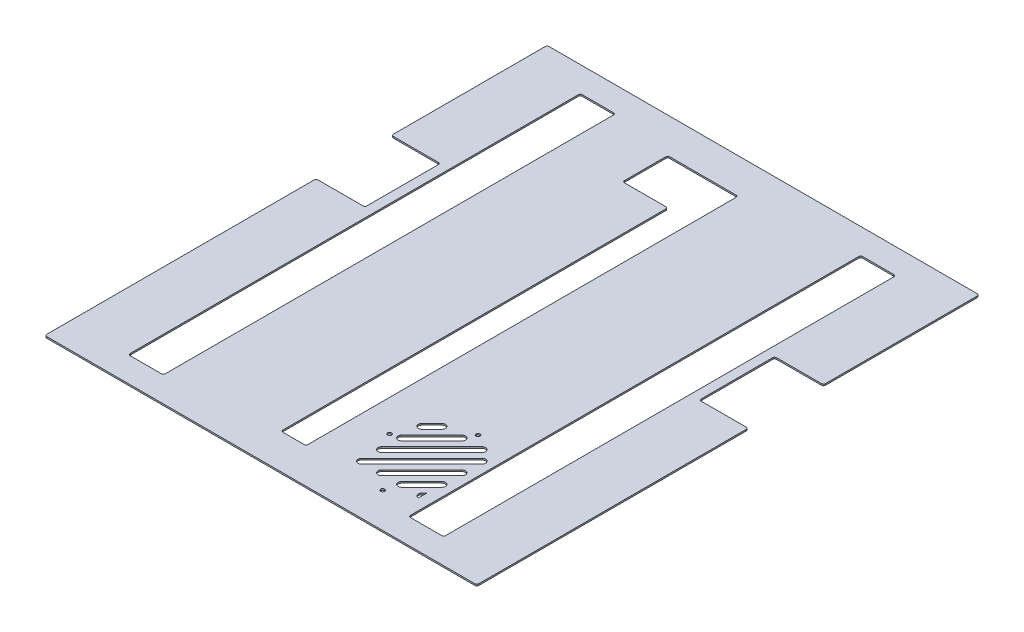
SolidWorks part; units mm, degrees
ref_plane "Front Plane" through (0, 0, 0) normal (0, 0, 1) x (1, 0, 0)
ref_plane "Top Plane" through (0, 0, 0) normal (0, 1, 0) x (1, 0, 0)
ref_plane "Right Plane" through (0, 0, 0) normal (1, 0, 0) x (0, 0, -1)
sketch "Sketch1" plane through (0, 0, 0) normal (0, 1, 0) x (1, 0, 0)
  line L1 (5911.0841, -8452.3124) -> (6341.0841, -8452.3124)
  line L2 (5911.0841, -8452.3124) -> (5911.0841, -8952.3124)
  line L3 (5911.0841, -8952.3124) -> (6341.0841, -8952.3124)
  line L4 (6341.0841, -8452.3124) -> (6341.0841, -8952.3124)
  dimension "D1" = 500
  dimension "D2" = 430
extrude "Boss-Extrude1" add sketch "Sketch1" along normal blind 1.5
sketch "Sketch2" plane through (0, 1.5, 0) normal (0, 1, 0) x (1, 0, 0)
  line L0 (5911.0841, -8452.3124) -> (5911.0841, -8952.3124) construction
  line L1 (5959.6841, -8682.3124) -> (5911.0841, -8682.3124)
  line L2 (5959.6841, -8682.3124) -> (5959.6841, -8607.3124)
  line L3 (5959.6841, -8607.3124) -> (5911.0841, -8607.3124)
  line L4 (5911.0841, -8682.3124) -> (5911.0841, -8607.3124)
  line L9 (6341.0841, -8952.3124) -> (6341.0841, -8452.3124) construction
  line L10 (6341.0841, -8682.3124) -> (6292.4841, -8682.3124)
  line L11 (6341.0841, -8682.3124) -> (6341.0841, -8607.3124)
  line L12 (6341.0841, -8607.3124) -> (6292.4841, -8607.3124)
  line L13 (6292.4841, -8682.3124) -> (6292.4841, -8607.3124)
  line L14 (6341.0841, -8452.3124) -> (5911.0841, -8452.3124) construction
  dimension "D1" = 48.6
  dimension "D2" = 75
  dimension "D3" = 75
  dimension "D4" = 48.6
  dimension "D5" = 155
extrude "Cut-Extrude1" cut sketch "Sketch2" against normal blind 10
sketch "Sketch3" plane through (0, 1.5, 0) normal (0, 1, 0) x (1, 0, 0)
  line L0 (5969.0841, -8541.6519) -> (5969.0841, -8927.3124)
  line L1 (6283.0841, -8927.3124) -> (6248.0841, -8927.3124)
  line L2 (6283.0841, -8927.3124) -> (6283.0841, -8477.3124)
  line L3 (6283.0841, -8477.3124) -> (6248.0841, -8477.3124)
  line L4 (6248.0841, -8927.3124) -> (6248.0841, -8477.3124)
  line L5 (5969.0841, -8477.3124) -> (6004.0841, -8477.3124)
  line L11 (5969.0841, -8927.3124) -> (6004.0841, -8927.3124)
  line L12 (6004.0841, -8477.3124) -> (6004.0841, -8927.3124)
  line L36 (5911.0841, -8682.3124) -> (5911.0841, -8952.3124) construction
  line L37 (6341.0841, -8952.3124) -> (6341.0841, -8682.3124) construction
  line L39 (6102.0841, -8487.3124) -> (6136.0841, -8487.3124)
  line L40 (6111.0841, -8532.3124) -> (6111.0841, -8917.3124)
  line L41 (6111.0841, -8917.3124) -> (6136.0841, -8917.3124)
  line L42 (6136.0841, -8487.3124) -> (6136.0841, -8917.3124)
  line L44 (6341.0841, -8452.3124) -> (5911.0841, -8452.3124) construction
  line L45 (5969.0841, -8477.3124) -> (5969.0841, -8541.6519)
  line L47 (5911.0841, -8952.3124) -> (6341.0841, -8952.3124) construction
  line L48 (6102.0841, -8487.3124) -> (6066.0841, -8487.3124)
  line L50 (6111.0841, -8532.3124) -> (6066.0841, -8532.3124)
  line L51 (6066.0841, -8487.3124) -> (6066.0841, -8532.3124)
  point P4 (6265.5841, -8477.3124)
  point P32 (6126.0841, -8452.3124)
  point P33 (6119.0841, -8487.3124)
  dimension "D15" = 35
  dimension "D22" = 45
  dimension "D1" = 35
  dimension "D3" = 35
  dimension "D4" = 25
  dimension "D5" = 25
  dimension "D6" = 58
  dimension "D7" = 45
  dimension "D8" = 58
  dimension "D9" = 205
  dimension "D10" = 35
  dimension "D11" = 200
  dimension "D20" = 25
  dimension "D21" = 25
extrude "Cut-Extrude2" cut sketch "Sketch3" against normal blind 10
sketch "Sketch4" plane through (0, 1.5, 0) normal (0, 1, 0) x (1, 0, 0)
  line L0 (6237.0841, -8848.0965) -> (6237.0841, -8858.0965) construction
  line L1 (6237.0841, -8898.0965) -> (6207.0841, -8898.0965) construction
  line L3 (6237.0841, -8833.0965) -> (6192.0841, -8833.0965) construction
  line L4 (6177.0841, -8898.0965) -> (6177.0841, -8848.0965) construction
  line L5 (5911.0841, -8952.3124) -> (6341.0841, -8952.3124) construction
  line L6 (6177.0841, -8898.0965) -> (6234.5841, -8840.5965)
  line L7 (6179.5841, -8885.5965) -> (6229.5841, -8835.5965)
  line L8 (6174.5841, -8880.5965) -> (6222.0841, -8833.0965)
  line L9 (6177.0841, -8898.0965) -> (6174.5841, -8900.5965)
  line L10 (6174.5841, -8880.5965) -> (6222.0841, -8833.0965)
  line L11 (6179.5841, -8865.5965) -> (6209.5841, -8835.5965)
  line L12 (6177.0841, -8898.0965) -> (6174.5841, -8900.5965) construction
  line L13 (6179.5841, -8865.5965) -> (6209.5841, -8835.5965)
  line L14 (6174.5841, -8860.5965) -> (6204.5841, -8830.5965)
  line L15 (6237.0841, -8888.0965) -> (6239.5841, -8885.5965)
  line L16 (6174.5841, -8860.5965) -> (6204.5841, -8830.5965)
  line L17 (6179.5841, -8845.5965) -> (6189.5841, -8835.5965)
  line L18 (6174.5841, -8840.5965) -> (6184.5841, -8830.5965)
  line L19 (6179.5841, -8885.5965) -> (6229.5841, -8835.5965)
  line L20 (6177.0841, -8878.0965) -> (6222.0841, -8833.0965)
  line L21 (6179.5841, -8865.5965) -> (6209.5841, -8835.5965)
  line L22 (6187.0841, -8898.0965) -> (6237.0841, -8848.0965)
  line L23 (6197.0841, -8898.0965) -> (6234.5841, -8860.5965)
  line L24 (6207.0841, -8898.0965) -> (6237.0841, -8868.0965)
  line L25 (6194.5841, -8900.5965) -> (6234.5841, -8860.5965)
  line L26 (6199.5841, -8905.5965) -> (6237.0841, -8868.0965)
  line L27 (6214.5841, -8900.5965) -> (6234.5841, -8880.5965)
  line L28 (6199.5841, -8905.5965) -> (6237.0841, -8868.0965)
  line L29 (6214.5841, -8900.5965) -> (6234.5841, -8880.5965)
  line L30 (6219.5841, -8905.5965) -> (6237.0841, -8888.0965)
  line L31 (6214.5841, -8900.5965) -> (6234.5841, -8880.5965)
  line L32 (6219.5841, -8905.5965) -> (6237.0841, -8888.0965)
  line L33 (6234.5841, -8900.5965) -> (6237.0841, -8898.0965)
  line L34 (6179.5841, -8905.5965) -> (6237.0841, -8848.0965)
  line L35 (6194.5841, -8900.5965) -> (6234.5841, -8860.5965)
  line L36 (6199.5841, -8905.5965) -> (6237.0841, -8868.0965)
  line L37 (6182.0841, -8833.0965) -> (6192.0841, -8833.0965) construction
  line L38 (6182.0841, -8833.0965) -> (6177.0841, -8833.0965) construction
  line L39 (6177.0841, -8863.0965) -> (6237.0841, -8863.0965) construction
  line L40 (6177.0841, -8838.0965) -> (6177.0841, -8833.0965) construction
  line L41 (6177.0841, -8838.0965) -> (6177.0841, -8848.0965) construction
  line L42 (6197.0841, -8898.0965) -> (6177.0841, -8898.0965) construction
  line L43 (6179.5841, -8865.5965) -> (6209.5841, -8835.5965)
  line L44 (6174.5841, -8860.5965) -> (6204.5841, -8830.5965)
  line L45 (6179.5841, -8845.5965) -> (6189.5841, -8835.5965)
  line L46 (6147.0841, -8878.0965) -> (6157.0841, -8868.0965) [skipped]
  line L47 (6147.0841, -8898.0965) -> (6157.0841, -8888.0965) [skipped]
  line L48 (6147.0841, -8888.0965) -> (6157.0841, -8878.0965) [skipped]
  line L49 (6237.0841, -8868.0965) -> (6239.5841, -8865.5965)
  line L52 (6222.0841, -8833.0965) -> (6224.5841, -8830.5965)
  line L54 (6237.0841, -8833.0965) -> (6237.0841, -8839.561) construction
  line L55 (6237.0841, -8898.0965) -> (6237.0841, -8906.6321)
  line L57 (6237.0841, -8888.0965) -> (6237.0841, -8898.0965) construction
  line L59 (6237.0841, -8848.0965) -> (6239.5841, -8845.5965)
  line L60 (6237.0841, -8868.0965) -> (6237.0841, -8879.561) construction
  arc A1 (6189.5841, -8835.5965) -> (6184.5841, -8830.5965) centre (6187.0841, -8833.0965) ccw
  arc A2 (6209.5841, -8835.5965) -> (6204.5841, -8830.5965) centre (6207.0841, -8833.0965) ccw
  arc A3 (6229.5841, -8835.5965) -> (6224.5841, -8830.5965) centre (6227.0841, -8833.0965) ccw
  arc A5 (6174.5841, -8840.5965) -> (6179.5841, -8845.5965) centre (6177.0841, -8843.0965) ccw
  arc A6 (6174.5841, -8860.5965) -> (6179.5841, -8865.5965) centre (6177.0841, -8863.0965) ccw
  arc A7 (6174.5841, -8880.5965) -> (6179.5841, -8885.5965) centre (6177.0841, -8883.0965) ccw
  arc A8 (6174.5841, -8900.5965) -> (6179.5841, -8905.5965) centre (6177.0841, -8903.0965) ccw
  arc A9 (6194.5841, -8900.5965) -> (6199.5841, -8905.5965) centre (6197.0841, -8903.0965) ccw
  arc A10 (6214.5841, -8900.5965) -> (6219.5841, -8905.5965) centre (6217.0841, -8903.0965) ccw
  arc A11 (6234.5841, -8900.5965) -> (6237.0841, -8906.6321) centre (6237.0841, -8903.0965) ccw
  arc A12 (6249.5841, -8835.5965) -> (6244.5841, -8830.5965) centre (6247.0841, -8833.0965) ccw [skipped]
  arc A13 (6239.5841, -8845.5965) -> (6234.5841, -8840.5965) centre (6237.0841, -8843.0965) ccw
  arc A14 (6239.5841, -8865.5965) -> (6234.5841, -8860.5965) centre (6237.0841, -8863.0965) ccw
  arc A15 (6239.5841, -8885.5965) -> (6234.5841, -8880.5965) centre (6237.0841, -8883.0965) ccw
  line M5 (6248.0841, -8927.3124) -> (6248.0841, -8477.3124)
  dimension "D8" = 4
  dimension "D1" = 65
  dimension "D3" = 54.2159
  dimension "D4" = 4
  dimension "D5" = 4
  dimension "D6" = 4
  dimension "D7" = 4
  dimension "D9" = 4
  dimension "D10" = 4
extrude "Cut-Extrude3" cut sketch "Sketch4" against normal blind 10 contours L27 A10 L30 M5 | L25 A9 L26 L24 L23 M5 | L8 A7 L7 A3 L52 L10 | L14 A6 L11 A2 | L18 A5 L17 A1 | L33 A11 M5 | L59 A13 L6 L9 A8 L34 region at (6202.0841, 1.5, 8858.0965) region at (6192.0841, 1.5, 8848.0965) region at (6227.0841, 1.5, 8893.0965) region at (6182.0841, 1.5, 8838.0965) region at (6217.0841, 1.5, 8883.0965) region at (6235.6369, 1.5, 8902.8482)
fillet "Fillet2" radius 2 12 edges at (6292.4841, 0.75, 8607.3124) (6341.0841, 0.75, 8607.3124) (6341.0841, 0.75, 8682.3124) (6292.4841, 0.75, 8682.3124) (5959.6841, 0.75, 8607.3124) (5959.6841, 0.75, 8682.3124) (5911.0841, 0.75, 8682.3124) (5911.0841, 0.75, 8607.3124) (5911.0841, 0.75, 8452.3124) (6341.0841, 0.75, 8452.3124) (6341.0841, 0.75, 8952.3124) (5911.0841, 0.75, 8952.3124)
fillet "Fillet3" radius 2 14 edges at (6004.0841, 0.75, 8927.3124) (5969.0841, 0.75, 8927.3124) (6004.0841, 0.75, 8477.3124) (5969.0841, 0.75, 8477.3124) (6283.0841, 0.75, 8927.3124) (6248.0841, 0.75, 8927.3124) (6283.0841, 0.75, 8477.3124) (6248.0841, 0.75, 8477.3124) (6136.0841, 0.75, 8917.3124) (6111.0841, 0.75, 8917.3124) (6136.0841, 0.75, 8487.3124) (6111.0841, 0.75, 8532.3124) (6066.0841, 0.75, 8487.3124) (6066.0841, 0.75, 8532.3124)
sketch "Sketch6" plane through (0, 1.5, 0) normal (0, 1, 0) x (1, 0, 0)
  line L0 (6177.0841, -8833.0965) -> (6248.0841, -8833.0965) construction
  line L1 (6248.0841, -8479.3124) -> (6248.0841, -8925.3124) construction
  line L2 (6248.0841, -8833.0965) -> (6248.0841, -8898.0738) construction
  line L3 (6248.0841, -8898.0738) -> (6177.0841, -8898.0965) construction
  line L4 (6177.0841, -8898.0965) -> (6177.0841, -8833.0965) construction
  line L5 (6177.0841, -8865.5965) -> (6248.0841, -8865.5852) construction
  line L6 (6212.5841, -8833.0965) -> (6212.5841, -8898.0852) construction
  line L7 (6212.5841, -8833.0965) -> (6212.5841, -8822.5908) construction
  line L8 (6177.0841, -8865.5965) -> (6167.5841, -8865.5965) construction
  line L9 (6212.5841, -8898.0852) -> (6212.5841, -8917.5908) construction
  line L10 (6237.0841, -8833.0965) -> (6237.0841, -8839.561) construction
  circle A0 centre (6212.5841, -8822.5908) radius 2
  circle A1 centre (6212.5841, -8917.5908) radius 2
  circle A2 centre (6167.5841, -8865.5965) radius 2
  dimension "D1" = 4
  dimension "D2" = 4
  dimension "D3" = 4
  dimension "D4" = 95
  dimension "D5" = 43
  dimension "D6" = 45
  dimension "D7" = 24.5
extrude "Cut-Extrude4" cut sketch "Sketch6" against normal blind 10
